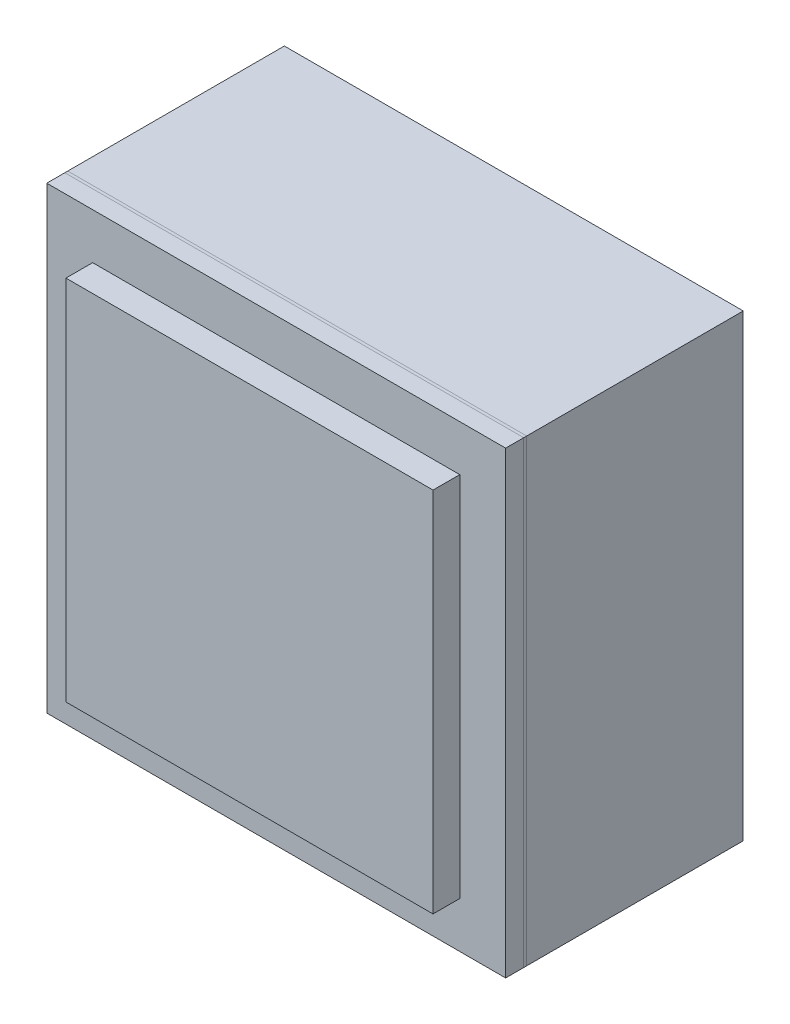
SolidWorks part; units mm, degrees
ref_plane "Front Plane" through (0, 0, 0) normal (0, 0, 1) x (1, 0, 0)
ref_plane "Top Plane" through (0, 0, 0) normal (0, 1, 0) x (1, 0, 0)
ref_plane "Right Plane" through (0, 0, 0) normal (1, 0, 0) x (0, 0, -1)
sketch "Sketch1" plane through (0, 0, 0) normal (1, 0, 0) x (0, 0, -1)
  line L1 (-7.493, 15.875) -> (7.493, 15.875)
  line L2 (-7.493, 15.875) -> (-7.493, -15.875)
  line L3 (-7.493, -15.875) -> (7.493, -15.875)
  line L4 (7.493, 15.875) -> (7.493, -15.875)
  line L5 (-7.493, 15.875) -> (7.493, -15.875) construction
  line L6 (-7.493, -15.875) -> (7.493, 15.875) construction
  line L7 (-7.493, 15.875) -> (-7.6962, 15.875)
  line L8 (-7.493, 15.875) -> (-7.493, -15.875)
  line L9 (-7.493, -15.875) -> (-7.6962, -15.875)
  line L10 (-7.6962, 15.875) -> (-7.6962, -15.875)
  line L11 (-7.6962, -15.875) -> (-8.9462, -15.875)
  line L12 (-7.6962, -15.875) -> (-7.6962, 15.875)
  line L13 (-7.6962, 15.875) -> (-8.9462, 15.875)
  line L14 (-8.9462, -15.875) -> (-8.9462, 15.875)
  line L15 (-8.9462, 12.7) -> (-10.795, 12.7)
  line L16 (-8.9462, 12.7) -> (-8.9462, -12.7)
  line L17 (-8.9462, -12.7) -> (-10.795, -12.7)
  line L18 (-10.795, 12.7) -> (-10.795, -12.7)
  line L19 (7.493, 15.875) -> (10.621, 15.875)
  line L20 (7.493, 15.875) -> (7.493, -15.875)
  line L21 (7.493, -15.875) -> (10.621, -15.875)
  line L22 (10.621, 15.875) -> (10.621, -15.875)
  line L23 (18.221, 15.875) -> (15.621, 15.875)
  line L24 (18.221, 15.875) -> (18.221, -15.875)
  line L25 (18.221, -15.875) -> (15.621, -15.875)
  line L26 (15.621, 15.875) -> (15.621, -15.875)
  line L27 (10.621, 15.875) -> (21.269, 15.875)
  line L28 (10.621, 15.875) -> (10.621, 13.375)
  line L29 (10.621, 13.375) -> (21.269, 13.375)
  line L30 (21.269, 15.875) -> (21.269, 13.375)
  line L31 (10.621, -15.875) -> (21.269, -15.875)
  line L32 (10.621, -15.875) -> (10.621, -13.375)
  line L33 (10.621, -13.375) -> (21.269, -13.375)
  line L34 (21.269, -15.875) -> (21.269, -13.375)
  point P0 (0, 0)
  point P26 (-10.795, 0)
  point P27 (0, 0)
  point P28 (15.621, 15.875)
  point P29 (18.221, -15.875)
  dimension "D1" = 31.75
  dimension "D2" = 3.302
  dimension "D3" = 14.986
  dimension "D4" = 8.128
  dimension "D5" = 0.2032
  dimension "D6" = 1.25
  dimension "D7" = 25.4
  dimension "D8" = 3.048
  dimension "D9" = 5
  dimension "D10" = 2.5
  dimension "D11" = 2.6
extrude "Boss-Extrude1" add sketch "Sketch1" along normal mid plane 31.75 contours L4 L1 L2 L3 region at (0, 0, 0)
extrude "Boss-Extrude2" add sketch "Sketch1<3>" along normal mid plane 31.75 separate body contours L14 L11 L10 L13 region at (0, 0, 8.3212)
sketch "Sketch1<3>" plane through (0, 0, 0) normal (1, 0, 0) x (0, 0, -1) same geometry as "Sketch1"
extrude "Boss-Extrude4" add sketch "Sketch1<6>" along normal mid plane 31.75 separate body contours L7 L10 L9 L2 region at (0, 0, 7.5946)
sketch "Sketch1<6>" plane through (0, 0, 0) normal (1, 0, 0) x (0, 0, -1) same geometry as "Sketch1"
extrude "Boss-Extrude5" add sketch "Sketch1<7>" along normal mid plane 25.4 separate body contours L15 L18 L17 L14 region at (0, 0, 9.8706)
sketch "Sketch1<7>" plane through (0, 0, 0) normal (1, 0, 0) x (0, 0, -1) same geometry as "Sketch1"
